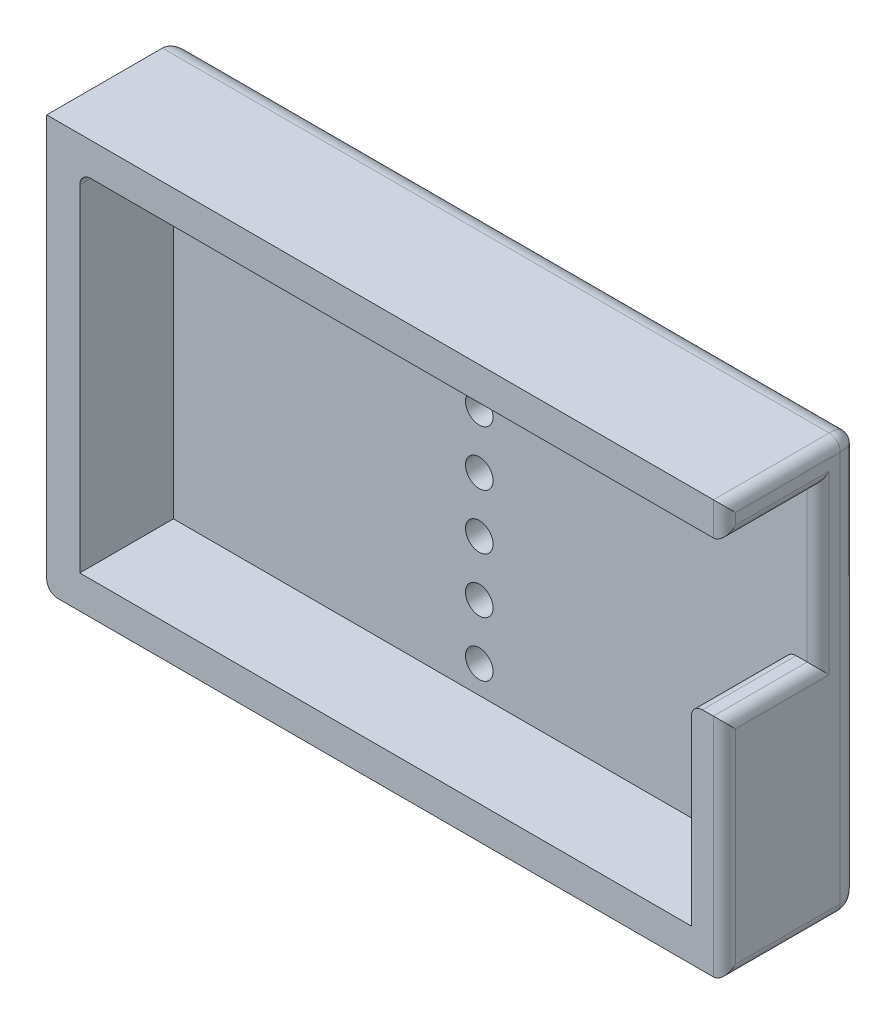
SolidWorks part; units mm, degrees
ref_plane "前视基准面" through (0, 0, 0) normal (0, 0, 1) x (1, 0, 0)
ref_plane "上视基准面" through (0, 0, 0) normal (0, 1, 0) x (1, 0, 0)
ref_plane "右视基准面" through (0, 0, 0) normal (1, 0, 0) x (0, 0, -1)
sketch "草图1" plane through (0, 0, 0) normal (0, 0, 1) x (1, 0, 0)
  line L0 (-30.75, -18.75) -> (-30.75, 18.75)
  line L1 (-27.75, -15.75) -> (27.75, -15.75)
  line L2 (-27.75, -15.75) -> (-27.75, 15.75)
  line L3 (-27.75, 15.75) -> (27.75, 15.75)
  line L4 (27.75, -15.75) -> (27.75, 15.75)
  line L5 (-27.75, -15.75) -> (27.75, 15.75) construction
  line L6 (-27.75, 15.75) -> (27.75, -15.75) construction
  line L7 (-30.75, 18.75) -> (30.75, 18.75)
  line L8 (30.75, -18.75) -> (30.75, 18.75)
  line L9 (-30.75, -18.75) -> (30.75, -18.75)
  line L10 (0, 13.75) -> (0, 15.75)
  line L11 (27.75, 15.75) -> (30.75, 15.75)
  line L12 (27.75, 15.75) -> (27.75, 1.75)
  line L13 (27.75, 1.75) -> (30.75, 1.75)
  line L14 (30.75, 15.75) -> (30.75, 1.75)
  line L15 (-15, 15.75) -> (15, 15.75)
  line L16 (-15, 15.75) -> (-15, 13.75)
  line L17 (-15, 13.75) -> (15, 13.75)
  line L18 (15, 15.75) -> (15, 13.75)
  circle A0 centre (18.85, -12.85) radius 2.2
  circle A1 centre (-18.65, -12.85) radius 2.2
  circle A2 centre (0, 11.75) radius 1.25
  circle A3 centre (0, 6.75) radius 1.25
  circle A4 centre (0, 1.75) radius 1.25
  circle A5 centre (0, -3.25) radius 1.25
  circle A6 centre (0, -8.25) radius 1.25
  circle A7 centre (0, -13.25) radius 1.25
  point P0 (0, 0)
  dimension "D5" = 4.4
  dimension "D6" = 2.9
  dimension "D7" = 8.9
  dimension "D13" = 2.5
  dimension "D1" = 55.5
  dimension "D2" = 31.5
  dimension "D4" = 14
  dimension "D8" = 2.9
  dimension "D9" = 9.1
  dimension "D10" = 2
  dimension "D11" = 30
  dimension "D14" = 7
  dimension "D3" = 3
  dimension "D12" = 6
extrude "凸台-拉伸1" add sketch "草图1" against normal blind 4 contours L1 L4 L3 L2 | L0 L9 L8 L7 L4 L1 L2 L3 | L4 L13 L8 L11 | A0 | A1 | L16 L15 L18 L17 region at (-30.0297, 0, 0) region at (29.25, 8.75, 0) region at (-0.0019, -0.2899, 0) region at (18.85, -12.85, 0) region at (-18.65, -12.85, 0)
extrude "凸台-拉伸2" add sketch "草图1<3>" along normal blind 8.5 contours L13 L4 L1 L2 L3 L11 L8 L7 L0 L9 region at (-30.0297, 0, 0)
sketch "草图1<3>" plane through (0, 0, 0) normal (0, 0, 1) x (1, 0, 0) same geometry as "草图1"
extrude "凸台-拉伸4" add sketch "草图1<5>" along normal blind 3.9 contours L16 L17 L10 L3 | L18 L3 L10 L17 region at (7.5, 14.75, 0) region at (-7.5, 14.75, 0)
sketch "草图1<5>" plane through (0, 0, 0) normal (0, 0, 1) x (1, 0, 0) same geometry as "草图1"
fillet "圆角1" radius 2 4 edges at (0, 18.75, -4) (-30.75, 0, -4) (0, -18.75, -4) (30.75, 0, -4)
fillet "圆角2" radius 1 13 edges at (30.1642, 18.1642, -3.4142) (-30.1642, -18.1642, -3.4142) (30.1642, -18.1642, -3.4142) (30.75, 17.25, 8.5) (30.75, 18.75, 3.25) (30.75, 15.75, 4.25) (30.75, 1.75, 4.25) (-30.75, -18.75, 3.25) (30.75, -18.75, 3.25) (-27.75, 15.75, 4.25) (27.75, 1.75, 4.25) (30.75, -8.5, 8.5) (30.75, 8.75, 0)
